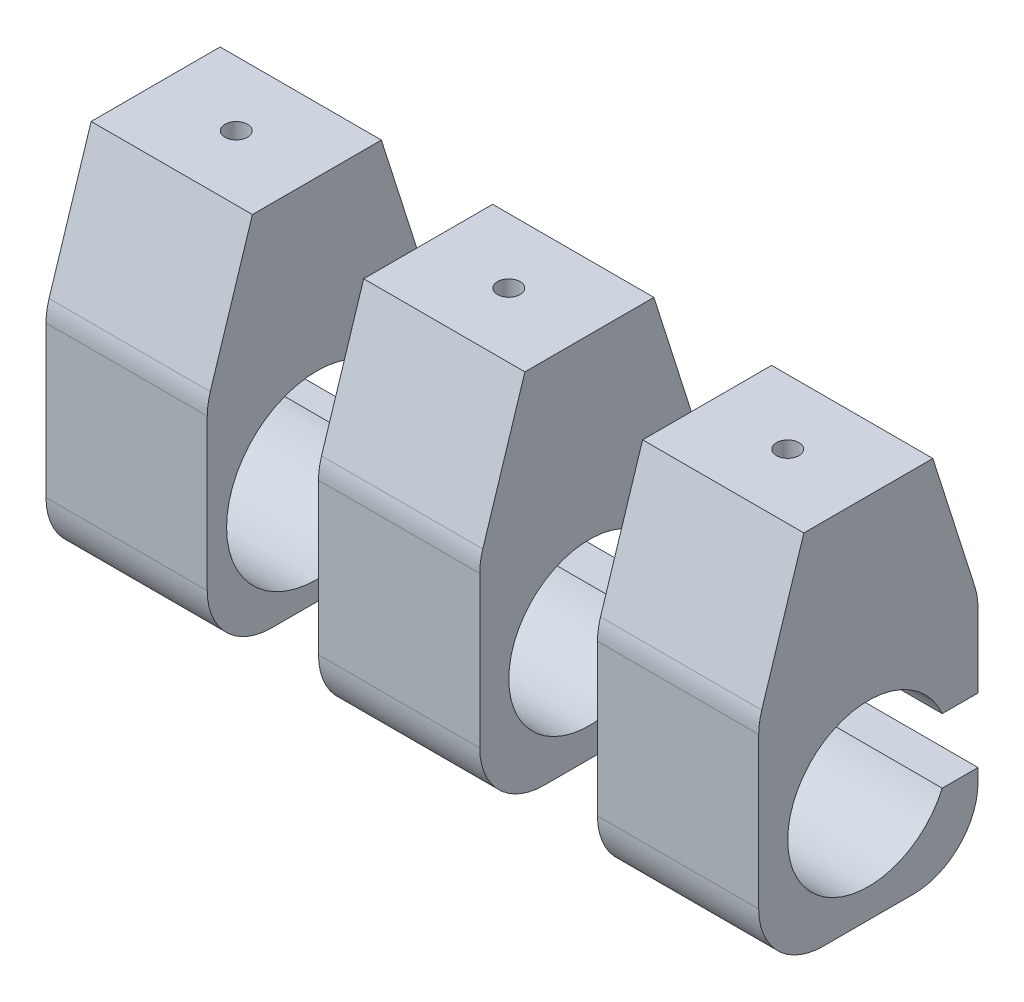
SolidWorks part; units mm, degrees
ref_plane "Front Plane" through (0, 0, 0) normal (0, 0, 1) x (1, 0, 0)
ref_plane "Top Plane" through (0, 0, 0) normal (0, 1, 0) x (1, 0, 0)
ref_plane "Right Plane" through (0, 0, 0) normal (1, 0, 0) x (0, 0, -1)
sketch "Sketch1" plane through (0, 0, 0) normal (1, 0, 0) x (0, 0, -1)
  line L0 (-10, 40) -> (10, 40)
  line L1 (10, 40) -> (17, 18)
  line L2 (17, 18) -> (17, -17)
  line L3 (17, -17) -> (-17, -17)
  line L4 (-17, -17) -> (-17, 18)
  line L5 (-17, 18) -> (-10, 40)
  line L6 (17, 5) -> (11.4564, 5)
  line L7 (17, -5) -> (11.4564, -5)
  circle A0 centre (0, 0) radius 14
  circle A1 centre (0, 0) radius 12.5
  point P6 (0, 40)
  point P15 (14.2282, -5)
  dimension "D2" = 25
  dimension "D3" = 28
  dimension "D1" = 20
  dimension "D4" = 17
  dimension "D5" = 35
  dimension "D6" = 17
  dimension "D7" = 22
  dimension "D8" = 10
extrude "zoom lense mount" add sketch "Sketch1" along normal blind 25 contours L5 L4 L3 L2 L1 L0 A0 region at (0, 15.201, 0.4463)
extrude "spec mount1" add sketch "Sketch1<4>" along normal blind 25 from offset 42.25 separate body contours A0 A1 | L5 L4 L3 L2 L1 L0 A0 region at (0, 15.201, 0.4463) region at (0, 5.3895, -12.2666)
sketch "Sketch1<4>" plane through (0, 0, 0) normal (1, 0, 0) x (0, 0, -1) same geometry as "Sketch1"
extrude "spec mount 2" add sketch "Sketch1<5>" along normal blind 25 from offset 85.5 separate body contours L5 L4 L3 L2 L1 L0 A0 | A0 A1 region at (0, 15.201, 0.4463) region at (0, 5.3895, -12.2666)
sketch "Sketch1<5>" plane through (0, 0, 0) normal (1, 0, 0) x (0, 0, -1) same geometry as "Sketch1"
fillet "Fillet1" radius 10 4 edges at (12.5, -17, -17) (12.5, 18, -17) (12.5, -17, 17) (12.5, 18, 17)
fillet "Fillet2" radius 10 4 edges at (54.75, -17, -17) (54.75, 18, -17) (54.75, -17, 17) (54.75, 18, 17)
fillet "Fillet3" radius 10 4 edges at (98, -17, -17) (98, 18, -17) (98, -17, 17) (98, 18, 17)
sketch "Sketch2" plane through (0, 40, 0) normal (0, 1, 0) x (1, 0, 0)
  line L0 (85.5, -10) -> (85.5, 10) construction
  circle A0 centre (98, 0) radius 1.75
  dimension "D2" = 3.5
  dimension "D1" = 12.5
extrude "Cut-Extrude1" cut sketch "Sketch2" against normal blind 30
sketch "Sketch3" plane through (0, 40, 0) normal (0, 1, 0) x (1, 0, 0)
  line L0 (67.25, -10) -> (67.25, 10) construction
  circle A0 centre (54.75, 0) radius 1.75
  dimension "D2" = 3.5
  dimension "D1" = 12.5
extrude "Cut-Extrude2" cut sketch "Sketch3" against normal blind 30
sketch "Sketch4" plane through (0, 40, 0) normal (0, 1, 0) x (1, 0, 0)
  line L0 (0, -10) -> (0, 10) construction
  circle A0 centre (12.5, 0) radius 1.75
  dimension "D2" = 3.5
  dimension "D1" = 12.5
extrude "Cut-Extrude3" cut sketch "Sketch4" against normal blind 30
